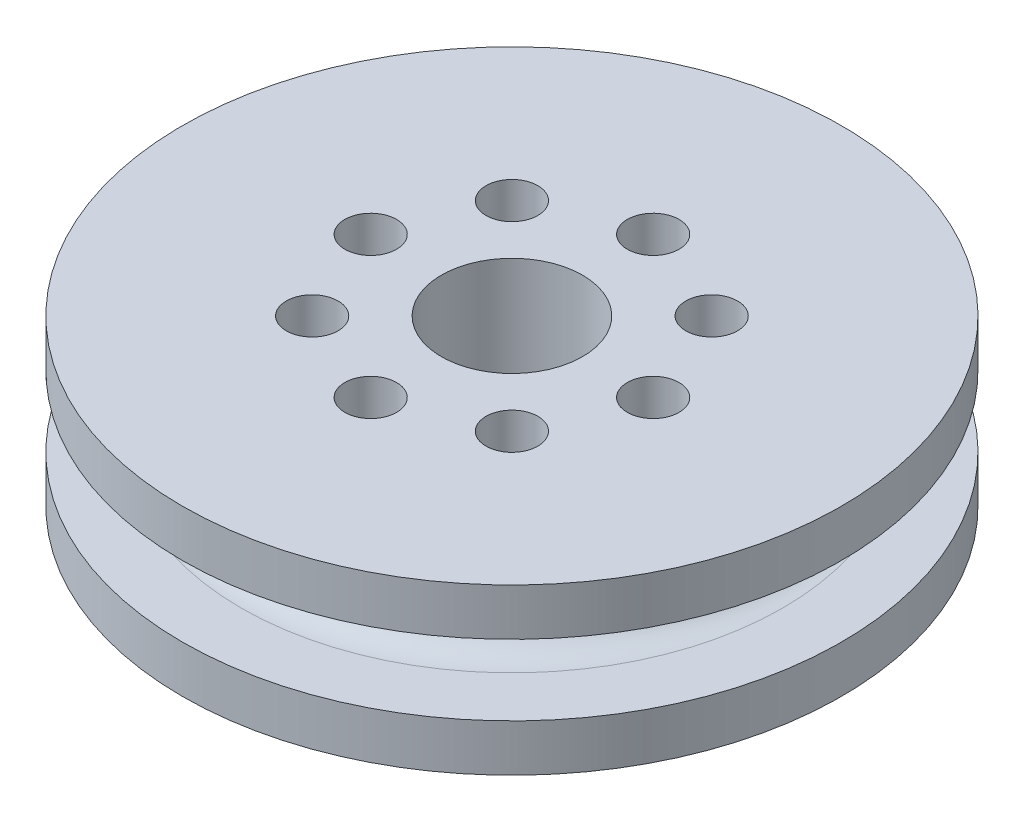
SolidWorks part; units mm, degrees
material "ABS"
ref_plane "正面" through (0, 0, 0) normal (0, 0, 1) x (1, 0, 0)
ref_plane "平面" through (0, 0, 0) normal (0, 1, 0) x (1, 0, 0)
ref_plane "右側面" through (0, 0, 0) normal (1, 0, 0) x (0, 0, -1)
sketch "ｽｹｯﾁ1" plane through (0, 0, 0) normal (0, 0, 1) x (1, 0, 0)
  line L0 (0, 0) -> (0, 6) construction
  line L1 (0, 3.5) -> (-14, 3.5)
  line L2 (-14, 3.5) -> (-14, 1.5)
  line L3 (-14, 1.5) -> (-11.5, 1.5)
  line L4 (-10, 0) -> (0, 0) construction
  line L5 (-14, -3.5) -> (-14, -1.5)
  line L6 (-14, -1.5) -> (-11.5, -1.5)
  line L7 (0, -3.5) -> (-14, -3.5)
  line L8 (0, 3.5) -> (0, -3.5)
  arc A0 (-11.5, 1.5) -> (-11.5, -1.5) centre (-11.5, 0) cw
  dimension "D1" = 3.5
  dimension "D2" = 1.5
  dimension "D3" = 10
  dimension "D4" = 2.5
revolve "回転1" add sketch "ｽｹｯﾁ1" angle 360 about L8
sketch "ｽｹｯﾁ2" plane through (0, -3.5, 0) normal (0, -1, 0) x (1, 0, 0)
  circle A0 centre (0, 0) radius 6 construction
  circle A1 centre (0, 0) radius 3
  circle A2 centre (0, 6) radius 1.1
  circle A3 centre (4.2426, 4.2426) radius 1.1
  circle A4 centre (6, 0) radius 1.1
  circle A5 centre (4.2426, -4.2426) radius 1.1
  circle A6 centre (0, -6) radius 1.1
  circle A7 centre (-4.2426, -4.2426) radius 1.1
  circle A8 centre (-6, 0) radius 1.1
  circle A9 centre (-4.2426, 4.2426) radius 1.1
  point P6 (-13.1403, 1.9729)
  point P7 (0, 0)
  point P23 (0, 0)
  dimension "D1" = 6
  dimension "D2" = 12
  dimension "D3" = 2.2
  dimension "D4" = 8
extrude "ｶｯﾄ - 押し出し1" cut sketch "ｽｹｯﾁ2" against normal through all
